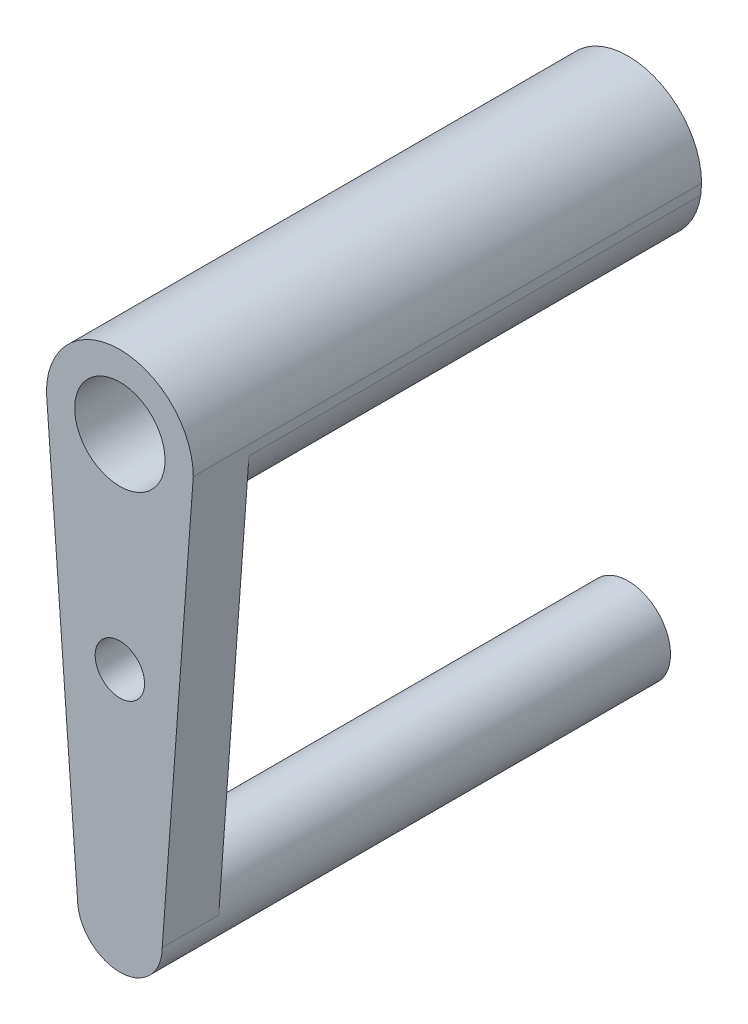
SolidWorks part; units mm, degrees
ref_plane "Front Plane" through (0, 0, 0) normal (0, 0, 1) x (1, 0, 0)
ref_plane "Top Plane" through (0, 0, 0) normal (0, 1, 0) x (1, 0, 0)
ref_plane "Right Plane" through (0, 0, 0) normal (1, 0, 0) x (0, 0, -1)
sketch "Sketch1" plane through (0, 0, 0) normal (0, 0, 1) x (1, 0, 0)
  line L0 (-3, -30) -> (-5.2, 0)
  line L5 (5.2, 0) -> (3, -30)
  circle A0 centre (0, 0) radius 3.2
  circle A1 centre (0, 0) radius 5.2
  circle A2 centre (0, -30) radius 3
  circle A3 centre (0, -14.4304) radius 1.75
  dimension "D1" = 6.4
  dimension "D4" = 30
  dimension "D3" = 6
  dimension "D5" = 3.5
  dimension "D2" = 2
extrude "Boss-Extrude1" add sketch "Sketch1" along normal blind 4 contours A2 | L5 A1 L0 A0 | A2 L5 A1 L0 A3 region at (-3.763, -15.3566, 0) region at (0, -30, 0) region at (-5.0255, -0.3685, 0)
extrude "Boss-Extrude2" add sketch "Sketch1<4>" against normal blind 32 contours L5 A1 L0 A0 | A2 region at (0, -30, 0) region at (-5.0255, -0.3685, 0)
sketch "Sketch1<4>" plane through (0, 0, 0) normal (0, 0, 1) x (1, 0, 0) same geometry as "Sketch1"
